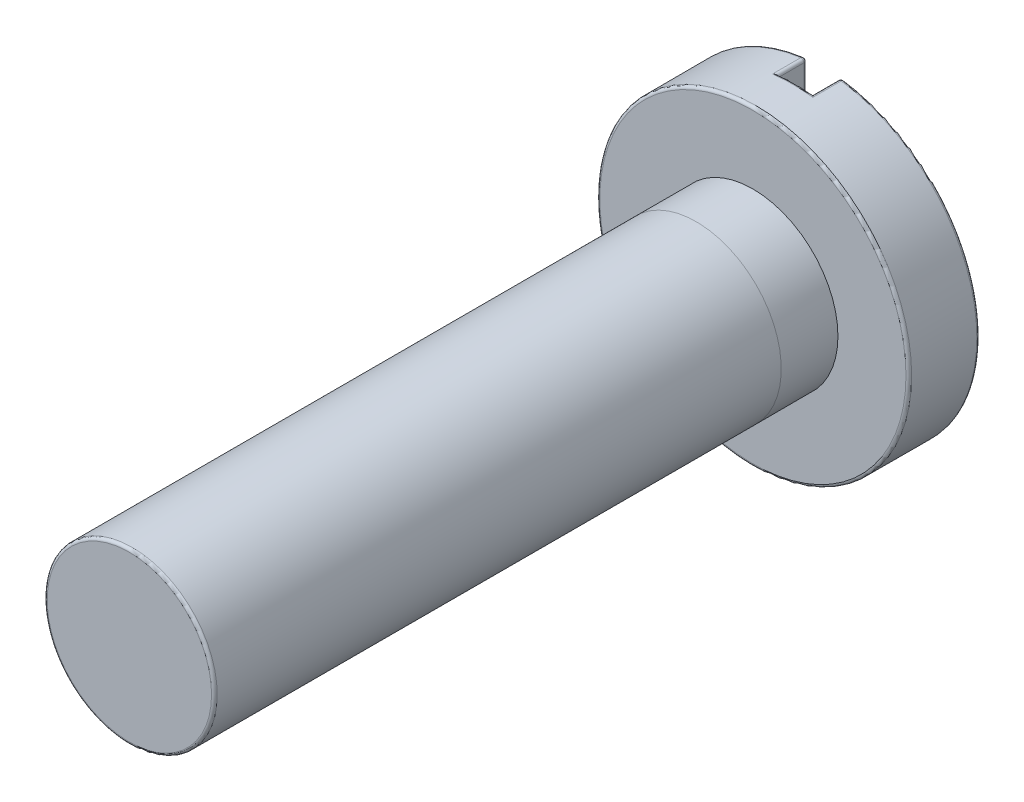
SolidWorks part; units mm, degrees
ref_plane "Front Plane" through (0, 0, 0) normal (0, 0, 1) x (1, 0, 0)
ref_plane "Top Plane" through (0, 0, 0) normal (0, 1, 0) x (1, 0, 0)
ref_plane "Right Plane" through (0, 0, 0) normal (1, 0, 0) x (0, 0, -1)
sketch "Sketch1" plane through (0, 0, 0) normal (0, 0, 1) x (1, 0, 0)
  circle A0 centre (0, 0) radius 1.5
  dimension "D1" = 3
extrude "Boss-Extrude1" add sketch "Sketch1" along normal blind 11 contours A0
sketch "Sketch2" plane through (0, 0, 0) normal (0, 0, 1) x (1, 0, 0)
  circle A2 centre (0, 0) radius 2.75
  circle A3 centre (0, 0) radius 2.75
  dimension "D1" = 1.25
extrude "Boss-Extrude2" add sketch "Sketch2" against normal blind 1.25
sketch "Sketch3" plane through (0, 0, -1.25) normal (0, 0, -1) x (-1, 0, 0)
  line L1 (-0.3, 4.1838) -> (0.3, 4.1838)
  line L2 (-0.3, 4.1838) -> (-0.3, -4.1838)
  line L3 (-0.3, -4.1838) -> (0.3, -4.1838)
  line L4 (0.3, 4.1838) -> (0.3, -4.1838)
  line L5 (-0.3, 4.1838) -> (0.3, -4.1838) construction
  line L6 (-0.3, -4.1838) -> (0.3, 4.1838) construction
  point P0 (0, 0)
  dimension "D1" = 0.6
extrude "Cut-Extrude1" cut sketch "Sketch3" against normal blind 0.5
fillet "Fillet1" radius 0.05 12 edges at (1.5, 0, 11) (2.75, 0, 0) (-0.3, -2.7336, -1) (0, -2.75, -0.75) (0.3, -2.7336, -1) (-0.3, 2.7336, -1) (0, 2.75, -0.75) (0.3, 2.7336, -1) (0.3, 0, -1.25) (2.75, 0, -1.25) (-2.75, 0, -1.25) (-0.3, 0, -1.25)
sketch "Sketch4" plane through (0, 0, 0) normal (0, 1, 0) x (1, 0, 0)
  line L0 (-4.2772, -1) -> (4.7645, -1)
  line L1 (-1.45, -11) -> (1.45, -11) construction
  dimension "D1" = 10
split line "Split Line1"
